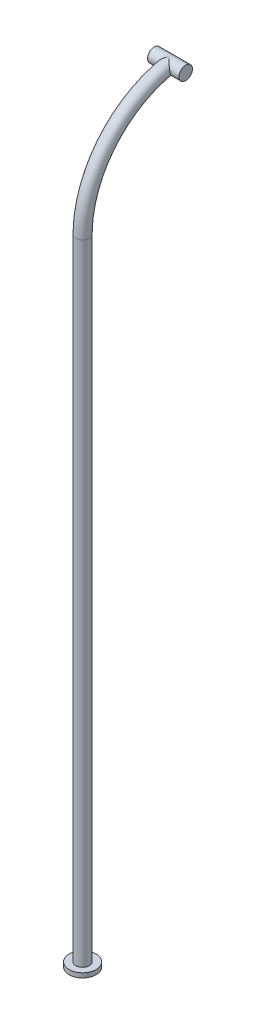
SolidWorks part; units mm, degrees
material "Nylon 101"
ref_plane "Front Plane" through (0, 0, 0) normal (0, 0, 1) x (1, 0, 0)
ref_plane "Top Plane" through (0, 0, 0) normal (0, 1, 0) x (1, 0, 0)
ref_plane "Right Plane" through (0, 0, 0) normal (1, 0, 0) x (0, 0, -1)
sketch "Sketch1" plane through (0, 0, 0) normal (0, 1, 0) x (1, 0, 0)
  circle A0 centre (0, 0) radius 1.5
extrude "Boss-Extrude1" add sketch "Sketch1" along normal blind 140
sketch "Sketch4" plane through (0, 0, 0) normal (0, -1, 0) x (1, 0, 0)
  circle A0 centre (0, 0) radius 3
extrude "Boss-Extrude4" add sketch "Sketch4" along normal blind 1
sketch "Sketch7" plane through (0, 140, 0) normal (0, 1, 0) x (1, 0, 0)
  line L0 (0, 0) -> (0, 44.3626) construction
  line L1 (0, 44.3626) -> (0, 23.5) construction
  line L2 (0, 23.5) -> (-42.5101, 23.5) construction
  line L3 (-42.5101, 23.5) -> (39.1951, 23.5) construction
  circle A0 centre (0, 0) radius 1.5
  dimension "D1" = 23.5
revolve "Revolve1" add sketch "Sketch7" angle 80 about L3 reverse direction yes
sketch "Sketch8" plane through (0, 0, 0) normal (1, 0, 0) x (0, 0, -1)
  line L0 (19.6797, 161.6658) -> (19.1588, 164.6202) construction
  circle A0 centre (19.4193, 163.143) radius 1.5
extrude "Boss-Extrude5" add sketch "Sketch8" along normal blind 3.5 and the other way blind 3.5
equation "\"4.5.00mm\"=10"
